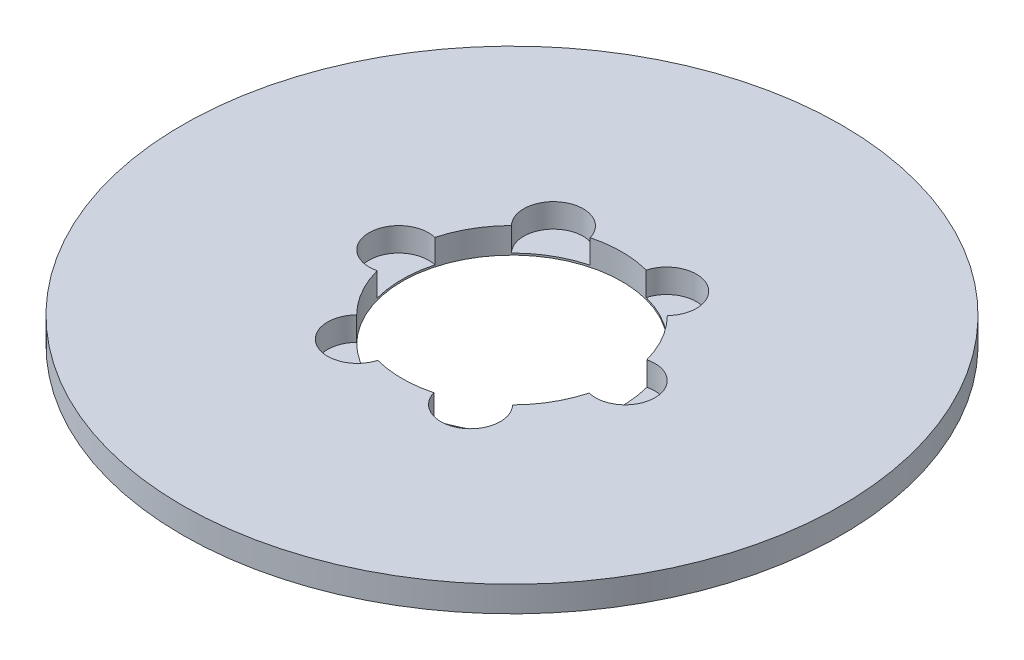
SolidWorks part; units mm, degrees
ref_plane "Front Plane" through (0, 0, 0) normal (0, 0, 1) x (1, 0, 0)
ref_plane "Top Plane" through (0, 0, 0) normal (0, 1, 0) x (1, 0, 0)
ref_plane "Right Plane" through (0, 0, 0) normal (1, 0, 0) x (0, 0, -1)
sketch "Sketch1" plane through (0, 0, 0) normal (0, 1, 0) x (1, 0, 0)
  circle A0 centre (0, 0) radius 90
  dimension "FLANGE_OD" = 180
extrude "Boss-Extrude1" add sketch "Sketch1" along normal blind 7
sketch "Sketch2" plane through (0, 0, 0) normal (0, 1, 0) x (1, 0, 0)
  circle A0 centre (0, 0) radius 30
  dimension "BORE_D" = 60
extrude "Cut-Extrude1" cut sketch "Sketch2" along normal through all
sketch "Sketch3" plane through (0, 7, 0) normal (0, 1, 0) x (1, 0, 0)
  circle A0 centre (0, 0) radius 30.9232 construction
  circle A1 centre (-30.9232, 0) radius 8.1179
  dimension "BOLT_D" = 16.2357
  dimension "BOLT_PCD" = 61.8463
extrude "Cut-Extrude2" cut sketch "Sketch3" against normal blind 6.5053
pattern_circular "CirPattern1" count 6 over 360 about axis through (0, 0, 0) along (0, 1, 0) of "Cut-Extrude2"
